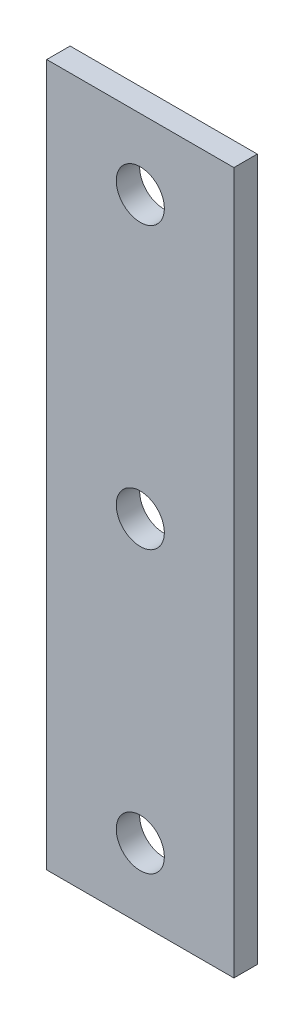
SolidWorks part; units mm, degrees
material "6061-T6 (SS)"
ref_plane "Front Plane" through (0, 0, 0) normal (0, 0, 1) x (1, 0, 0)
ref_plane "Top Plane" through (0, 0, 0) normal (0, 1, 0) x (1, 0, 0)
ref_plane "Right Plane" through (0, 0, 0) normal (1, 0, 0) x (0, 0, -1)
sketch "Sketch2" plane through (0, 0, 0) normal (0, 0, 1) x (1, 0, 0)
  line L1 (-6.35, -23.8125) -> (6.35, -23.8125)
  line L2 (-6.35, -23.8125) -> (-6.35, 23.8125)
  line L3 (-6.35, 23.8125) -> (6.35, 23.8125)
  line L4 (6.35, -23.8125) -> (6.35, 23.8125)
  line L5 (-6.35, -23.8125) -> (6.35, 23.8125) construction
  line L6 (-6.35, 23.8125) -> (6.35, -23.8125) construction
  point P0 (0, 0)
  dimension "D1" = 47.625
  dimension "D2" = 12.7
base flange "Base-Flange1" sketch "Sketch2" thickness 1.5875 reverse thickness direction no parameters "D1"=254
sketch "Sketch7" plane through (0, 0, 0) normal (0, 0, 1) x (1, 0, 0)
  line L0 (0, 23.8125) -> (0, -23.8125) construction
  line L1 (6.35, 23.8125) -> (-6.35, 23.8125) construction
  line L2 (-6.35, -23.8125) -> (6.35, -23.8125) construction
  line L3 (-6.35, 0) -> (6.35, 0) construction
  line L4 (-6.35, 23.8125) -> (-6.35, -23.8125) construction
  line L5 (6.35, -23.8125) -> (6.35, 23.8125) construction
hole_wizard "#4 Clearance Hole1" positions "Sketch9" profile "Sketch8" hole size "#4" standard "ANSI Inch" end condition through all
sketch "Sketch9" plane through (0, 0, 0) normal (0, 0, 1) x (1, 0, 0)
  line L0 (0, 23.8125) -> (0, -23.8125) construction
  point P0 (0, 0)
  point P3 (0, 19.05)
  point P7 (0, -19.05)
  dimension "D1" = 19.05
  dimension "D2" = 19.05
sketch "Sketch8" plane through (0, 0, 0) normal (1, 0, 0) x (0, -1, 0)
  line L0 (0, 0) -> (0, 1.5875)
  line L1 (0, 1.5875) -> (1.6319, 1.5875)
  line L2 (1.6319, 1.5875) -> (1.6319, 0)
  line L5 (1.6319, 0) -> (0, 0)
  line L11 (0, -6.35) -> (0, 107.95) construction
  dimension "Thru Hole Dia." = 3.2639
  dimension "Thru Hole Depth" = 1.5875
sketch "Bend-Lines1" [suppressed] plane through (0, 0, 0) normal (0, 1, 0) x (1, 0, 0)
sketch "Bounding-Box1" [suppressed] plane through (0, 0, 0) normal (0, 1, 0) x (1, 0, 0)
sheet metal parameters "Sheet-Metal1" thickness 1.5875 parameters "D1"=254
flat pattern "Flat-Pattern1" [suppressed]
sketch "Bend-Lines2" plane through (0, 0, 0) normal (0, 1, 0) x (1, 0, 0)
sketch3d "Bounding-Box2" [suppressed]
  line L0 (-6.35, 23.8125, 0) -> (-6.35, -23.8125, 0) construction
  line L1 (6.35, 23.8125, 0) -> (6.35, -23.8125, 0) construction
  line L2 (-6.35, 23.8125, 0) -> (6.35, 23.8125, 0) construction
  line L3 (-6.35, -23.8125, 0) -> (6.35, -23.8125, 0) construction
sheet metal parameters "Sheet-Metal2" thickness 1.5875 parameters "D1"=254
flat pattern "Flat-Pattern1"
sketch "Bend-Lines2" plane through (0, 0, 0) normal (0, 1, 0) x (1, 0, 0)
sketch3d "Bounding-Box2" [suppressed]
  line L0 (6.35, 23.8125, 0) -> (6.35, -23.8125, 0) construction
  line L1 (-6.35, 23.8125, 0) -> (-6.35, -23.8125, 0) construction
  line L2 (6.35, 23.8125, 0) -> (-6.35, 23.8125, 0) construction
  line L3 (6.35, -23.8125, 0) -> (-6.35, -23.8125, 0) construction
